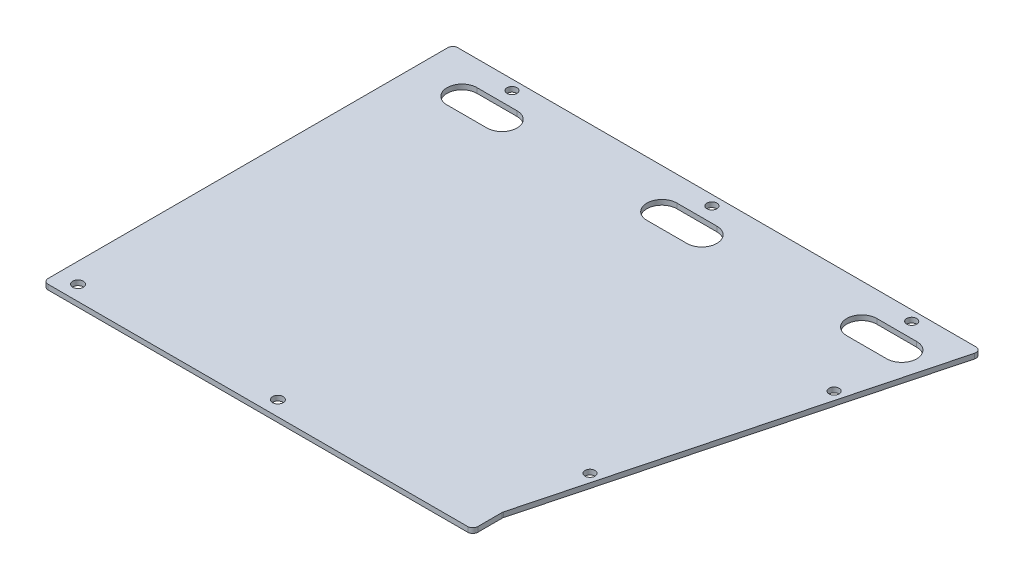
SolidWorks part; units mm, degrees
material "PC High Viscosity"
ref_plane "Front Plane" through (0, 0, 0) normal (0, 0, 1) x (1, 0, 0)
ref_plane "Top Plane" through (0, 0, 0) normal (0, 1, 0) x (1, 0, 0)
ref_plane "Right Plane" through (0, 0, 0) normal (1, 0, 0) x (0, 0, -1)
sketch "Sketch1" plane through (0, 0, 0) normal (0, 1, 0) x (1, 0, 0)
  line L0 (0, 0) -> (273.05, 0)
  line L1 (273.05, 0) -> (273.05, 19.05)
  line L2 (273.05, 19.05) -> (336.55, 260.35)
  line L3 (336.55, 260.35) -> (0, 260.35)
  line L4 (0, 260.35) -> (0, 0)
  dimension "D1" = 260.35
  dimension "D2" = 241.3
  dimension "D3" = 273.05
  dimension "D4" = 336.55
extrude "Boss-Extrude1" add sketch "Sketch1" along normal blind 3.175
fillet "Fillet1" radius 3.175 5 edges at (336.55, 1.5875, -260.35) (0, 1.5875, -260.35) (0, 1.5875, 0) (273.05, 1.5875, 0) (273.05, 1.5875, -19.05)
sketch "Sketch2" plane through (0, 3.175, 0) normal (0, 1, 0) x (1, 0, 0)
  line L0 (311.7215, 190.9534) -> (279.4009, 68.1349) construction
  line L1 (43.9782, 254) -> (297.9782, 254) construction
  line L2 (273.1545, 19.4472) -> (335.5018, 256.367) construction
  line L4 (298.1873, 139.5231) -> (304.3282, 137.9071) construction
  line L5 (332.4314, 260.35) -> (3.175, 260.35) construction
  point P0 (43.9782, 254)
  point P1 (170.9782, 254)
  point P2 (297.9782, 254)
  point P3 (279.4009, 68.1349)
  point P5 (311.7215, 190.9534)
  point P10 (167.8032, 260.35)
  point P15 (304.3282, 137.9071)
  dimension "D1" = 6.35
  dimension "D2" = 6.35
  dimension "D3" = 127
  dimension "D4" = 254
  dimension "D5" = 3.175
  dimension "D6" = 53.1812
hole_wizard "1/4 (0.25) Diameter Hole1" positions "Sketch3" profile "Sketch4" hole size "1/4" standard "ANSI Inch" end condition through all
sketch "Sketch3" plane through (0, 3.175, 0) normal (0, 1, 0) x (1, 0, 0)
  line L0 (43.9782, 254) -> (297.9782, 254) construction
  point P0 (43.9782, 254)
  point P3 (170.9782, 254)
  point P7 (297.9782, 254)
  point P10 (311.7215, 190.9534)
  point P17 (279.4009, 68.1349)
sketch "Sketch4" plane through (43.9782, 3.175, -254) normal (1, 0, 0) x (0, 0, 1)
  line L0 (0, 0) -> (0, 3.175)
  line L1 (0, 3.175) -> (3.175, 3.175)
  line L2 (3.175, 3.175) -> (3.175, 0)
  line L5 (3.175, 0) -> (0, 0)
  line L11 (0, -6.35) -> (0, 107.95) construction
  dimension "Thru Hole Dia." = 6.35
  dimension "Thru Hole Depth" = 3.175
sketch "Sketch5" plane through (0, 3.175, 0) normal (0, 1, 0) x (1, 0, 0)
  line L0 (0, 257.175) -> (0, 3.175) construction
  line L1 (3.175, 0) -> (269.875, 0) construction
  point P0 (12.7, 9.525)
  point P1 (139.7, 9.525)
  dimension "D1" = 127
  dimension "D2" = 12.7
  dimension "D3" = 9.525
hole_wizard "17/64 (0.26563) Diameter Hole1" positions "Sketch6" profile "Sketch7" hole size "17/64" standard "ANSI Inch" end condition through all
sketch "Sketch6" plane through (0, 3.175, 0) normal (0, 1, 0) x (1, 0, 0)
  point P0 (12.7, 9.525)
  point P3 (139.7, 9.525)
sketch "Sketch7" plane through (12.7, 3.175, -9.525) normal (1, 0, 0) x (0, 0, 1)
  line L0 (0, 0) -> (0, 3.175)
  line L1 (0, 3.175) -> (3.3735, 3.175)
  line L2 (3.3735, 3.175) -> (3.3735, 0)
  line L5 (3.3735, 0) -> (0, 0)
  line L11 (0, -6.35) -> (0, 107.95) construction
  dimension "Thru Hole Dia." = 6.747
  dimension "Thru Hole Depth" = 3.175
sketch "Sketch9" plane through (0, 3.175, 0) normal (0, 1, 0) x (1, 0, 0)
  line L0 (31.2782, 234.95) -> (56.6782, 234.95) construction
  line L1 (31.2782, 244.475) -> (56.6782, 244.475)
  line L2 (31.2782, 225.425) -> (56.6782, 225.425)
  line L3 (158.2782, 234.95) -> (183.6782, 234.95) construction
  line L4 (158.2782, 244.475) -> (183.6782, 244.475)
  line L5 (158.2782, 225.425) -> (183.6782, 225.425)
  line L6 (285.2782, 234.95) -> (310.6782, 234.95) construction
  line L7 (285.2782, 244.475) -> (310.6782, 244.475)
  line L8 (285.2782, 225.425) -> (310.6782, 225.425)
  circle A0 centre (297.9782, 254) radius 3.175 construction
  circle A1 centre (170.9782, 254) radius 3.175 construction
  circle A2 centre (43.9782, 254) radius 3.175 construction
  circle A3 centre (297.9782, 254) radius 3.175
  circle A4 centre (170.9782, 254) radius 3.175
  circle A5 centre (43.9782, 254) radius 3.175
  arc A6 (31.2782, 244.475) -> (31.2782, 225.425) centre (31.2782, 234.95) ccw
  arc A7 (56.6782, 225.425) -> (56.6782, 244.475) centre (56.6782, 234.95) ccw
  arc A8 (158.2782, 244.475) -> (158.2782, 225.425) centre (158.2782, 234.95) ccw
  arc A9 (183.6782, 225.425) -> (183.6782, 244.475) centre (183.6782, 234.95) ccw
  arc A10 (285.2782, 244.475) -> (285.2782, 225.425) centre (285.2782, 234.95) ccw
  arc A11 (310.6782, 225.425) -> (310.6782, 244.475) centre (310.6782, 234.95) ccw
  point P11 (43.9782, 234.95)
  point P17 (170.9782, 234.95)
  point P24 (297.9782, 234.95)
  dimension "D2" = 9.525
  dimension "D1" = 25.4
  dimension "D3" = 19.05
extrude "Cut-Extrude1" cut sketch "Sketch9" against normal through all
